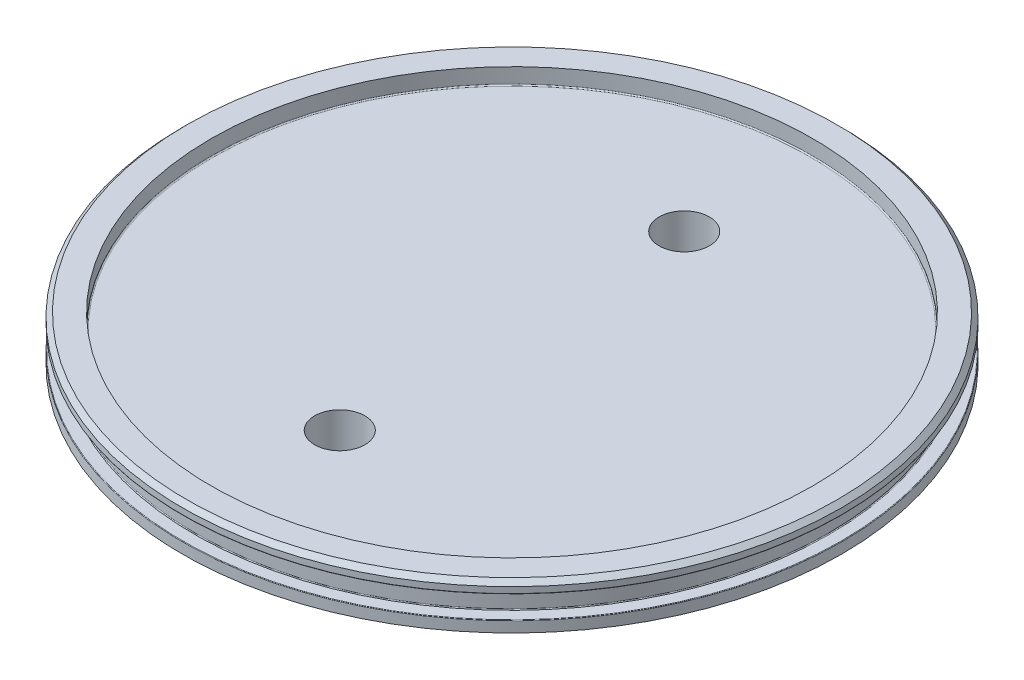
SolidWorks part; units mm, degrees
material "6061-T6 (SS)"
ref_plane "Front Plane" through (0, 0, 0) normal (0, 0, 1) x (1, 0, 0)
ref_plane "Top Plane" through (0, 0, 0) normal (0, 1, 0) x (1, 0, 0)
ref_plane "Right Plane" through (0, 0, 0) normal (1, 0, 0) x (0, 0, -1)
sketch "Sketch1" plane through (0, 0, 0) normal (0, 0, 1) x (1, 0, 0)
  line L0 (0, 48.1922) -> (0, -25.6743) construction
  line L1 (0, 0) -> (72.898, 0)
  line L2 (72.898, 0) -> (72.898, 2.4638)
  line L3 (72.898, 2.4638) -> (70.0532, 2.4638)
  line L4 (70.0532, 2.4638) -> (70.0532, 7.4422)
  line L5 (70.0532, 7.4422) -> (72.898, 7.4422)
  line L6 (72.898, 7.4422) -> (72.898, 9.906)
  line L7 (72.898, 9.906) -> (66.548, 9.906)
  line L8 (66.548, 9.906) -> (66.548, 6.35)
  line L9 (66.548, 6.35) -> (0, 6.35)
  line L10 (0, 6.35) -> (0, 0)
  dimension "D1" = 145.796
  dimension "D2" = 4.9784
  dimension "D3" = 2.8448
  dimension "D4" = 9.906
  dimension "D5" = 6.35
  dimension "D6" = 6.35
revolve "Revolve1" add sketch "Sketch1" angle 360 about L0
sketch "Sketch6" plane through (0, 0, 0) normal (0, -1, 0) x (1, 0, 0)
  circle A0 centre (0, 0) radius 66.04
  dimension "D1" = 132.08
extrude "Boss-Extrude1" add sketch "Sketch6" along normal blind 2.54
fillet "CNC ID Fillet" radius 0.1778 3 edges at (-70.0532, 7.4422, 0) (-70.0532, 2.4638, 0) (66.04, 0, 0)
fillet "CNC OD Fillet" radius 0.127 3 edges at (-72.898, 7.4422, 0) (-72.898, 2.4638, 0) (66.04, -2.54, 0)
chamfer "CNC Chamfers" distance 1.016 angle 45 1 edges at (-72.898, 9.906, 0)
fillet "CNC Bore Fillet" radius 0.254 1 edges at (-66.548, 6.35, 0)
hole_wizard "Pipe Tap Drill for 1/4 Tap - Relief Valve" positions "Sketch13" profile "Sketch14" hole size "1/4" standard "ANSI Inch" end condition through all
sketch "Sketch13" plane through (0, -2.54, 0) normal (0, -1, 0) x (-1, 0, 0)
  point P4 (0, 38.1)
  dimension "D1" = 38.1
sketch "Sketch14" plane through (0, -2.54, -38.1) normal (1, 0, 0) x (0, 0, -1)
  line L0 (0, 0) -> (0, 12.446)
  line L1 (0, 12.446) -> (5.5626, 12.446)
  line L2 (5.5626, 12.446) -> (5.5626, 0)
  line L5 (5.5626, 0) -> (0, 0)
  line L11 (0, -6.35) -> (0, 107.95) construction
  dimension "Thru Hole Dia." = 11.1252
  dimension "Thru Hole Depth" = 12.446
hole_wizard "Pipe Tap Drill for 1/4 Tap - Vent Valve" positions "Sketch15" profile "Sketch16" hole size "1/4" standard "ANSI Inch" end condition through all
sketch "Sketch15" plane through (0, -2.54, 0) normal (0, -1, 0) x (-1, 0, 0)
  point P4 (0, -38.1)
  dimension "D1" = 38.1
sketch "Sketch16" plane through (0, -2.54, 38.1) normal (1, 0, 0) x (0, 0, -1)
  line L0 (0, 0) -> (0, 12.446)
  line L1 (0, 12.446) -> (5.5626, 12.446)
  line L2 (5.5626, 12.446) -> (5.5626, 0)
  line L5 (5.5626, 0) -> (0, 0)
  line L11 (0, -6.35) -> (0, 107.95) construction
  dimension "Thru Hole Dia." = 11.1252
  dimension "Thru Hole Depth" = 12.446
